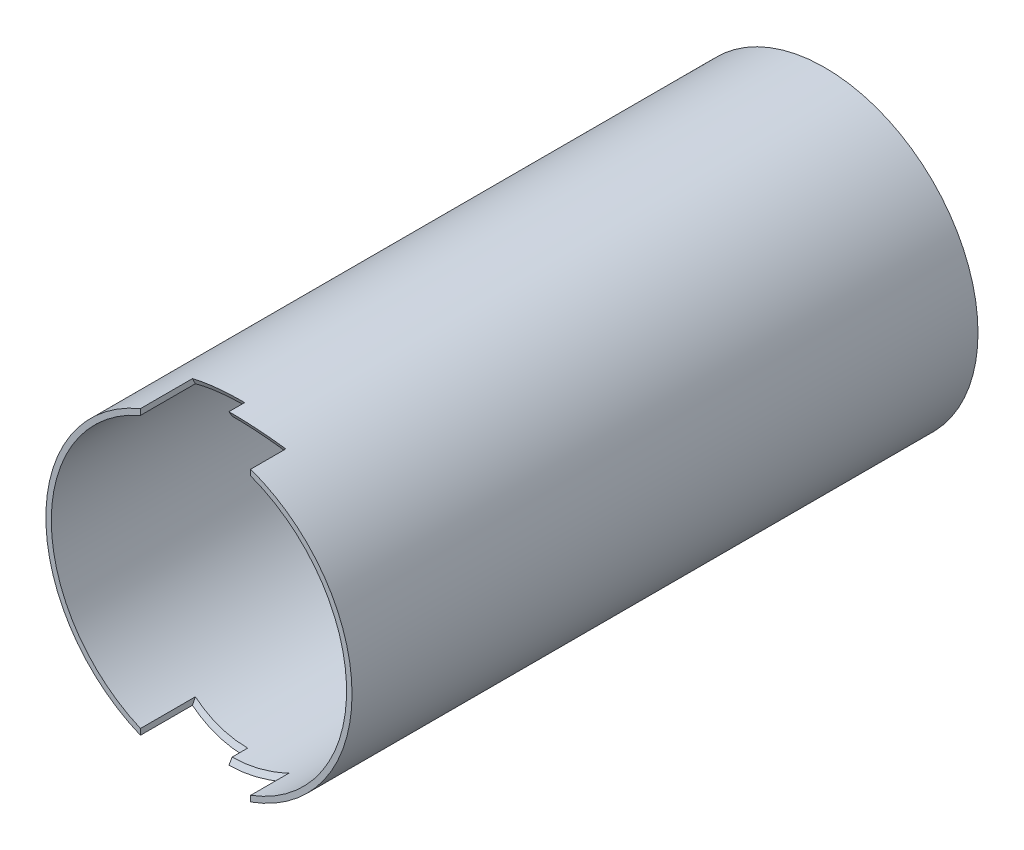
SolidWorks part; units mm, degrees
ref_plane "Front Plane" through (0, 0, 0) normal (1, 0, 0) x (0, 1, 0)
ref_plane "Top Plane" through (0, 0, 0) normal (0, 0, 1) x (0, 1, 0)
ref_plane "Right Plane" through (0, 0, 0) normal (0, 1, 0) x (-1, 0, 0)
sketch "Sketch1" plane through (0, 0, 0) normal (0, 0, 1) x (0, 1, 0)
  circle A0 centre (0, 0) radius 22.5
  circle A1 centre (0, 0) radius 21.7
  dimension "D1" = 45
  dimension "D2" = 0.8
extrude "Boss-Extrude1" add sketch "Sketch1" along normal blind 92
sketch "Sketch3" plane through (0, 0, 0) normal (1, 0, 0) x (0, 1, 0)
  line L0 (0, 0) -> (0, 125) construction
  circle A0 centre (0, 125) radius 45.65
  circle A1 centre (0, 125) radius 43.65
  dimension "D1" = 125
  dimension "D2" = 91.3
  dimension "D3" = 87.3
extrude "Cut-Extrude1" cut sketch "Sketch3" against normal blind 8.6 contours A0
extrude "Cut-Extrude2" cut sketch "Sketch3<3>" along normal blind 7.6 contours A1
sketch "Sketch3<3>" plane through (0, 0, 0) normal (1, 0, 0) x (0, 1, 0) same geometry as "Sketch3"
